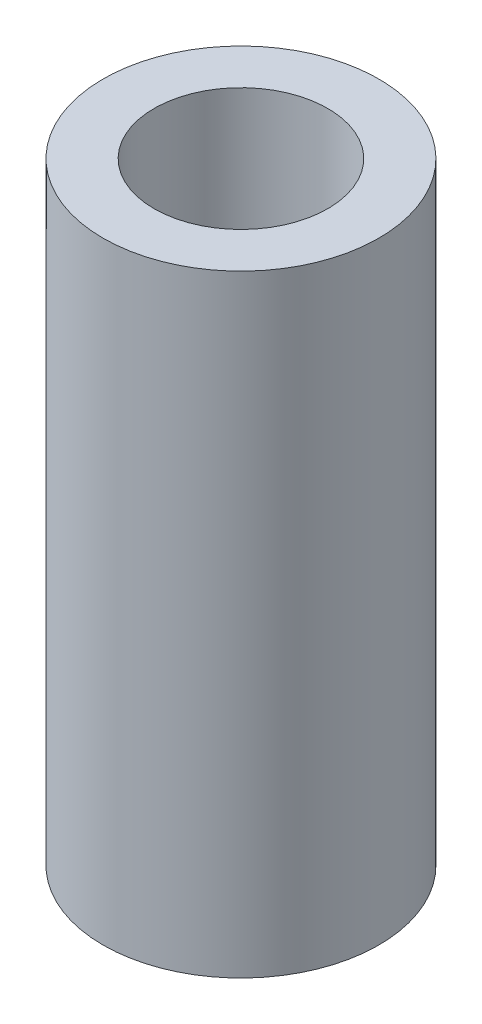
SolidWorks part; units mm, degrees
ref_plane "Front Plane" through (0, 0, 0) normal (0, 0, 1) x (1, 0, 0)
ref_plane "Top Plane" through (0, 0, 0) normal (0, 1, 0) x (1, 0, 0)
ref_plane "Right Plane" through (0, 0, 0) normal (1, 0, 0) x (0, 0, -1)
sketch "Sketch1" plane through (0, 0, 0) normal (0, 1, 0) x (1, 0, 0)
  circle A0 centre (0, 0) radius 6.35
  dimension "D1" = 12.7
extrude "Boss-Extrude1" add sketch "Sketch1" along normal blind 28.194
sketch "Sketch2" plane through (0, 28.194, 0) normal (0, 1, 0) x (1, 0, 0)
  circle A0 centre (0, 0) radius 4
  dimension "D1" = 8
sketch "Sketch3" plane through (0, 28.194, 0) normal (0, 1, 0) x (1, 0, 0)
  circle A0 centre (0, 0) radius 4
  dimension "D1" = 8
extrude "Cut-Extrude2" cut sketch "Sketch3" against normal through all
